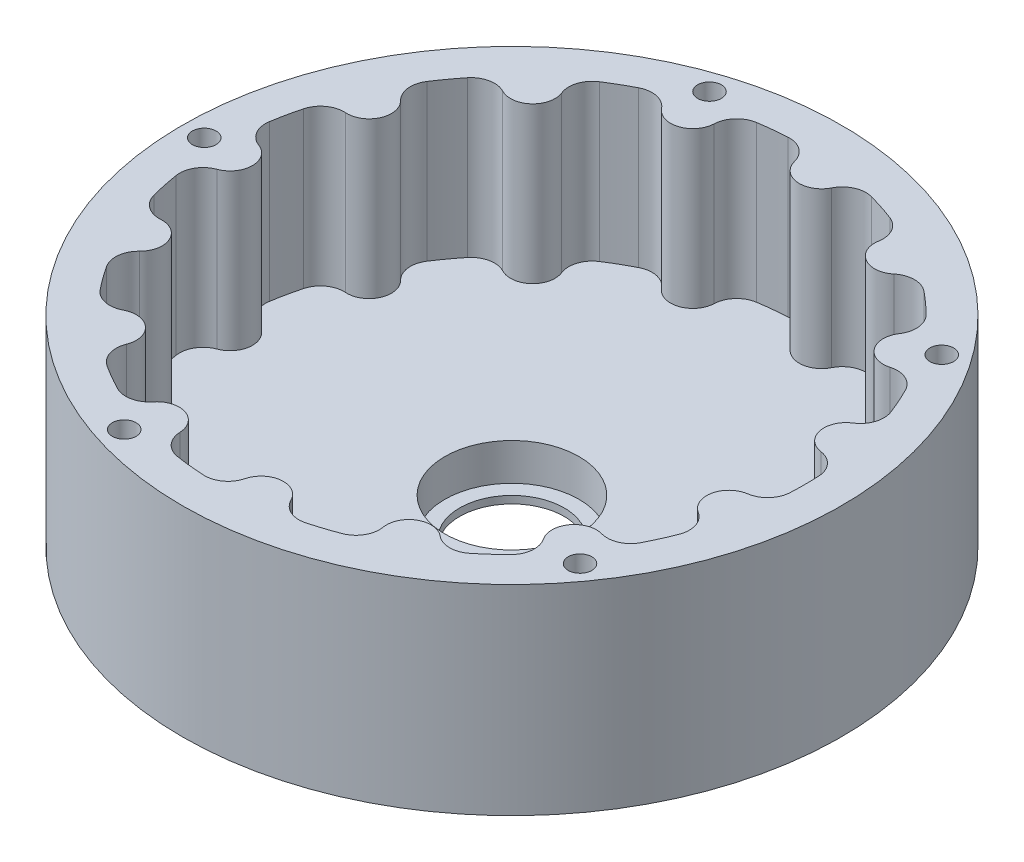
SolidWorks part; units mm, degrees
ref_plane "Front Plane" through (0, 0, 0) normal (0, 0, 1) x (1, 0, 0)
ref_plane "Top Plane" through (0, 0, 0) normal (0, 1, 0) x (1, 0, 0)
ref_plane "Right Plane" through (0, 0, 0) normal (1, 0, 0) x (0, 0, -1)
sketch "Sketch1" plane through (0, 0, 0) normal (0, 1, 0) x (1, 0, 0)
  line L0 (0, 0) -> (-38, 0) construction
  line L1 (-38.6368, 8.2125) -> (0, 0) construction
  circle A0 centre (0, 0) radius 44.45
  arc A1 (-36.9604, -2.8141) -> (-36.9604, 2.8141) centre (-38, 0) ccw
  arc A2 (-36.9604, 2.8141) -> (-38.9946, 6.2987) centre (-35.8602, 5.7924) cw
  arc A3 (-38.9946, 6.2987) -> (-38.6368, 8.2125) centre (0, 0) cw
  arc A4 (-38.9946, -6.2987) -> (-38.6368, -8.2125) centre (0, 0) ccw
  arc A5 (-36.9604, -2.8141) -> (-38.9946, -6.2987) centre (-35.8602, -5.7924) ccw
  arc A6 (-38.1852, 10.1064) -> (-38.6368, 8.2125) centre (0, 0) ccw
  arc A7 (-34.9096, 12.4623) -> (-38.1852, 10.1064) centre (-35.1159, 9.294) ccw
  arc A8 (-34.9096, 12.4623) -> (-32.6204, 17.604) centre (-34.7147, 15.456) ccw
  arc A9 (-32.6204, 17.604) -> (-33.0614, 21.6147) centre (-30.4039, 19.8773) cw
  arc A10 (-33.0614, 21.6147) -> (-31.9562, 23.2175) centre (0, 0) cw
  arc A11 (-30.7733, 24.764) -> (-31.9562, 23.2175) centre (0, 0) ccw
  arc A12 (-26.8226, 25.5839) -> (-30.7733, 24.764) centre (-28.2997, 22.7734) ccw
  arc A13 (-26.8226, 25.5839) -> (-22.64, 29.35) centre (-25.427, 28.2395) ccw
  arc A14 (-22.64, 29.35) -> (-21.4116, 33.1933) centre (-19.6906, 30.5252) cw
  arc A15 (-21.4116, 33.1933) -> (-19.75, 34.208) centre (0, 0) cw
  arc A16 (-18.0404, 35.1396) -> (-19.75, 34.208) centre (0, 0) ccw
  arc A17 (-14.0978, 34.2818) -> (-18.0404, 35.1396) centre (-16.5903, 32.3151) ccw
  arc A18 (-14.0978, 34.2818) -> (-8.745, 36.0211) centre (-11.7426, 36.1401) ccw
  arc A19 (-8.745, 36.0211) -> (-6.0596, 39.0324) centre (-5.5725, 35.895) cw
  arc A20 (-6.0596, 39.0324) -> (-4.1289, 39.2836) centre (0, 0) cw
  arc A21 (-2.1881, 39.4393) -> (-4.1289, 39.2836) centre (0, 0) ccw
  arc A22 (1.0647, 37.0521) -> (-2.1881, 39.4393) centre (-2.0123, 36.2692) ccw
  arc A23 (1.0647, 37.0521) -> (6.6621, 36.4638) centre (3.9721, 37.7918) ccw
  arc A24 (6.6621, 36.4638) -> (10.3402, 38.1226) centre (9.5091, 35.0583) cw
  arc A25 (10.3402, 38.1226) -> (12.2062, 37.5667) centre (0, 0) cw
  arc A26 (14.0425, 36.9196) -> (12.2062, 37.5667) centre (0, 0) ccw
  arc A27 (16.0431, 33.4157) -> (14.0425, 36.9196) centre (12.9137, 33.952) ccw
  arc A28 (16.0431, 33.4157) -> (20.9173, 30.6016) centre (19, 32.909) ccw
  arc A29 (20.9173, 30.6016) -> (24.9521, 30.6209) centre (22.9465, 28.1596) cw
  arc A30 (24.9521, 30.6209) -> (26.4307, 29.3542) centre (0, 0) cw
  arc A31 (27.845, 28.0162) -> (26.4307, 29.3542) centre (0, 0) ccw
  arc A32 (28.2475, 24.0015) -> (27.845, 28.0162) centre (25.6068, 25.7642) ccw
  arc A33 (28.2475, 24.0015) -> (31.5557, 19.4481) centre (30.7426, 22.3358) ccw
  arc A34 (31.5557, 19.4481) -> (35.2495, 17.8247) centre (32.4162, 16.3919) cw
  arc A35 (35.2495, 17.8247) -> (36.085, 16.0661) centre (0, 0) cw
  arc A36 (36.8329, 14.2685) -> (36.085, 16.0661) centre (0, 0) ccw
  arc A37 (35.5677, 10.4371) -> (36.8329, 14.2685) centre (33.8723, 13.1216) ccw
  arc A38 (35.5677, 10.4371) -> (36.7378, 4.9319) centre (37.1696, 7.9006) ccw
  arc A39 (36.7378, 4.9319) -> (39.452, 1.9464) centre (36.2809, 1.7899) cw
  arc A40 (39.452, 1.9464) -> (39.5, 0) centre (0, 0) cw
  arc A41 (39.452, -1.9464) -> (39.5, 0) centre (0, 0) ccw
  arc A42 (36.7378, -4.9319) -> (39.452, -1.9464) centre (36.2809, -1.7899) ccw
  arc A43 (36.7378, -4.9319) -> (35.5677, -10.4371) centre (37.1696, -7.9006) ccw
  arc A44 (35.5677, -10.4371) -> (36.8329, -14.2685) centre (33.8723, -13.1216) cw
  arc A45 (36.8329, -14.2685) -> (36.085, -16.0661) centre (0, 0) cw
  arc A46 (35.2495, -17.8247) -> (36.085, -16.0661) centre (0, 0) ccw
  arc A47 (31.5557, -19.4481) -> (35.2495, -17.8247) centre (32.4162, -16.3919) ccw
  arc A48 (31.5557, -19.4481) -> (28.2475, -24.0015) centre (30.7426, -22.3358) ccw
  arc A49 (28.2475, -24.0015) -> (27.845, -28.0162) centre (25.6068, -25.7642) cw
  arc A50 (27.845, -28.0162) -> (26.4307, -29.3542) centre (0, 0) cw
  arc A51 (24.9521, -30.6209) -> (26.4307, -29.3542) centre (0, 0) ccw
  arc A52 (20.9173, -30.6016) -> (24.9521, -30.6209) centre (22.9465, -28.1596) ccw
  arc A53 (20.9173, -30.6016) -> (16.0431, -33.4157) centre (19, -32.909) ccw
  arc A54 (16.0431, -33.4157) -> (14.0425, -36.9196) centre (12.9137, -33.952) cw
  arc A55 (14.0425, -36.9196) -> (12.2062, -37.5667) centre (0, 0) cw
  arc A56 (10.3402, -38.1226) -> (12.2062, -37.5667) centre (0, 0) ccw
  arc A57 (6.6621, -36.4638) -> (10.3402, -38.1226) centre (9.5091, -35.0583) ccw
  arc A58 (6.6621, -36.4638) -> (1.0647, -37.0521) centre (3.9721, -37.7918) ccw
  arc A59 (1.0647, -37.0521) -> (-2.1881, -39.4393) centre (-2.0123, -36.2692) cw
  arc A60 (-2.1881, -39.4393) -> (-4.1289, -39.2836) centre (0, 0) cw
  arc A61 (-6.0596, -39.0324) -> (-4.1289, -39.2836) centre (0, 0) ccw
  arc A62 (-8.745, -36.0211) -> (-6.0596, -39.0324) centre (-5.5725, -35.895) ccw
  arc A63 (-8.745, -36.0211) -> (-14.0978, -34.2818) centre (-11.7426, -36.1401) ccw
  arc A64 (-14.0978, -34.2818) -> (-18.0404, -35.1396) centre (-16.5903, -32.3151) cw
  arc A65 (-18.0404, -35.1396) -> (-19.75, -34.208) centre (0, 0) cw
  arc A66 (-21.4116, -33.1933) -> (-19.75, -34.208) centre (0, 0) ccw
  arc A67 (-22.64, -29.35) -> (-21.4116, -33.1933) centre (-19.6906, -30.5252) ccw
  arc A68 (-22.64, -29.35) -> (-26.8226, -25.5839) centre (-25.427, -28.2395) ccw
  arc A69 (-26.8226, -25.5839) -> (-30.7733, -24.764) centre (-28.2997, -22.7734) cw
  arc A70 (-30.7733, -24.764) -> (-31.9562, -23.2175) centre (0, 0) cw
  arc A71 (-33.0614, -21.6147) -> (-31.9562, -23.2175) centre (0, 0) ccw
  arc A72 (-32.6204, -17.604) -> (-33.0614, -21.6147) centre (-30.4039, -19.8773) ccw
  arc A73 (-32.6204, -17.604) -> (-34.9096, -12.4623) centre (-34.7147, -15.456) ccw
  arc A74 (-34.9096, -12.4623) -> (-38.1852, -10.1064) centre (-35.1159, -9.294) cw
  arc A75 (-38.1852, -10.1064) -> (-38.6368, -8.2125) centre (0, 0) cw
  dimension "D1" = 88.9
  dimension "D3" = 3
  dimension "D4" = 39.5
  dimension "D5" = 3.175
  dimension "D2" = 38
  dimension "D6" = 12
  dimension "D7" = 15
extrude "Boss-Extrude1" add sketch "Sketch1" along normal blind 27 contours A0 A74 A75 A4 A5 A1 A2 A3 A6 A7 A8 A9 A10 A11 A12 A13 A14 A15 A16 A17 A18 A19 A20 A21 A22 A23 A24 A25 A26 A27 A28 A29 A30 A31 A32 A33 A34 A35 A36 A37 A38 A39 A40 A41 A42 A43 A44 A45 A46 A47 region at (-43.1928, 0, 0)
extrude "Boss-Extrude2" add sketch "Sketch1<3>" along normal blind 6 contours A0 A74 A75 A4 A5 A1 A2 A3 A6 A7 A8 A9 A10 A11 A12 A13 A14 A15 A16 A17 A18 A19 A20 A21 A22 A23 A24 A25 A26 A27 A28 A29 A30 A31 A32 A33 A34 A35 A36 A37 A38 A39 A40 A41 A42 A43 A44 A45 A46 A47 | A75 A74 A73 A72 A71 A70 A69 A68 A67 A66 A65 A64 A63 A62 A61 A60 A59 A58 A57 A56 A55 A54 A53 A52 A51 A50 A49 A48 A47 A46 A45 A44 A43 A42 A41 A40 A39 A38 A37 A36 A35 A34 A33 A32 A31 A30 A29 A28 A27 A26 A25 region at (-43.1928, 0, 0) region at (0, 0, 0)
sketch "Sketch1<3>" plane through (0, 0, 0) normal (0, 1, 0) x (1, 0, 0) same geometry as "Sketch1"
sketch "Sketch2" plane through (0, 0, 0) normal (0, 1, 0) x (1, 0, 0)
  circle A0 centre (0, 0) radius 9.05
  circle A1 centre (0, 0) radius 7.05
  dimension "D1" = 18.1
extrude "Cut-Extrude1" cut sketch "Sketch2" along normal through all contours A1 region at (0, 0, 0)
extrude "Cut-Extrude2" cut sketch "Sketch2<3>" along normal through all from offset 1 contours A0 A1 region at (-8.794, 0, 0)
sketch "Sketch2<3>" plane through (0, 0, 0) normal (0, 1, 0) x (1, 0, 0) same geometry as "Sketch2"
hole_wizard "M3 Clearance Hole1" positions "Sketch4" profile "Sketch6" hole size "M3" standard "ANSI Metric" end condition through all
sketch "Sketch4" plane through (0, 27, 0) normal (0, 1, 0) x (1, 0, 0)
  line L2 (-41.5, 0) -> (0, 0) construction
  point P10 (-41.5, 0)
  dimension "D1" = 41.5
sketch "Sketch6" plane through (-41.5, 27, 0) normal (1, 0, 0) x (0, 0, 1)
  line L0 (0, 0) -> (0, 27)
  line L1 (0, 27) -> (1.6, 27)
  line L2 (1.6, 27) -> (1.6, 0)
  line L5 (1.6, 0) -> (0, 0)
  line L11 (0, -6.35) -> (0, 107.95) construction
  dimension "Thru Hole Dia." = 3.2
  dimension "Thru Hole Depth" = 27
pattern_circular "CirPattern1" count 5 over 360 about axis through (0, 27, 0) along (0, -1, 0) of "M3 Clearance Hole1" reverse direction yes
equation "\"Ratio\"= 15"
equation "\"Hull Diameter\"= 3.5in"
equation "\"Fixed Ring Diameter\"= 76"
equation "\"Fixed Pin Diameter\"= 6"
equation "\"Output Ring Diameter\"= 40"
equation "\"Output Pin Diameter\"= 6"
equation "\"Disk Bearing Inner Diameter\"= 9"
equation "\"Disk Bearing Outer Diameter\"= 17"
equation "\"Disk Bearing Height\"= 5"
equation "\"Shaft Bearing Inner Diameter\"= 15"
equation "\"Shaft Bearing Outer Diameter\"= 21"
equation "\"Shaft Bearing Height\"= 4"
equation "\"Eccentricity\"= 1.5"
equation "\"Disk Height\"= 8"
equation "\"Disk Spacing\"= 5"
equation "\"Hull Height\"= 40"
equation "\"Shaft End Bearing Inner Diameter\"= 12"
equation "\"Shaft End Bearing Outer Diameter\"= 18"
equation "\"Shaft End Bearing Height\"= 4"
equation "\"Output Bearing Inner Diameter\"= 55"
equation "\"Output Bearing Outer Diameter\"= 72"
equation "\"Outer Bearing Height\"= 9"
equation "\"D1@Sketch1\"=\"Hull Diameter\""
equation "\"D3@Sketch1\"=\"Fixed Pin Diameter\"/2"
equation "\"D2@Sketch1\"=\"Fixed Ring Diameter\"/2"
equation "\"D4@Sketch1\"=(\"Fixed Ring Diameter\"/2)+(\"Eccentricity\")"
equation "\"D6@Sketch1\"=180/(\"Ratio\")"
equation "\"D7@Sketch1\"=\"Ratio\""
equation "\"D1@Sketch2\"=\"Shaft End Bearing Outer Diameter\"+0.1"
